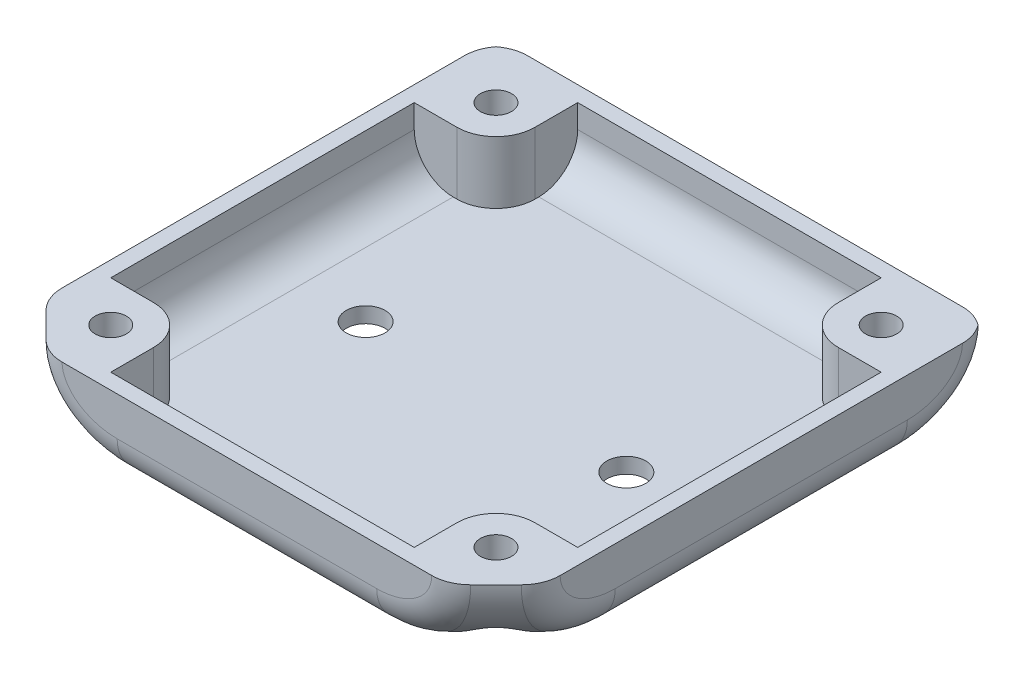
SolidWorks part; units mm, degrees
ref_plane "Front Plane" through (0, 0, 0) normal (0, 0, 1) x (1, 0, 0)
ref_plane "Top Plane" through (0, 0, 0) normal (0, 1, 0) x (1, 0, 0)
ref_plane "Right Plane" through (0, 0, 0) normal (1, 0, 0) x (0, 0, -1)
sketch "Sketch1" plane through (0, 0, 0) normal (0, 1, 0) x (1, 0, 0)
  line L1 (-32, -32) -> (32, -32)
  line L2 (-32, -32) -> (-32, 32)
  line L3 (-32, 32) -> (32, 32)
  line L4 (32, -32) -> (32, 32)
  line L5 (-32, -32) -> (32, 32) construction
  line L6 (-32, 32) -> (32, -32) construction
  point P0 (0, 0)
  dimension "D1" = 64
  dimension "D2" = 64
extrude "Boss-Extrude1" add sketch "Sketch1" along normal blind 2
sketch "Sketch2" plane through (0, 2, 0) normal (0, 1, 0) x (1, 0, 0)
  line L1 (-32, -32) -> (32, -32)
  line L2 (-32, -32) -> (-32, 32)
  line L3 (-32, 32) -> (32, 32)
  line L4 (32, -32) -> (32, 32)
  line L5 (-32, -32) -> (32, 32) construction
  line L6 (-32, 32) -> (32, -32) construction
  line L7 (-30, -30) -> (30, -30)
  line L8 (-30, -30) -> (-30, 30)
  line L9 (-30, 30) -> (30, 30)
  line L10 (30, -30) -> (30, 30)
  line L11 (-30, -30) -> (30, 30) construction
  line L12 (-30, 30) -> (30, -30) construction
  point P0 (0, 0)
  point P7 (0, 0)
  dimension "D1" = 2
  dimension "D2" = 2
extrude "Boss-Extrude2" add sketch "Sketch2" along normal blind 8
sketch "Sketch3" plane through (0, 0, 0) normal (0, -1, 0) x (1, 0, 0)
  line L0 (32, 32) -> (32, -32) construction
  line L5 (-22, 32) -> (-32, 32)
  line L7 (-32, 32) -> (32, 32) construction
  line L14 (32, 32) -> (22, 32)
  line L15 (-32, 22) -> (-22, 32)
  line L16 (22, 32) -> (32, 22)
  line L22 (32, 32) -> (27, 27) construction
  line L23 (-27, 27) -> (-32, 32) construction
  line L27 (-32, 22) -> (-32, 32)
  line L30 (32, 22) -> (32, 32)
  point P0 (0, 0)
  point P10 (0, 0)
  point P18 (0, 0)
extrude "Cut-Extrude1" cut sketch "Sketch3" against normal blind 10
sketch "Sketch4" plane through (0, 0, 0) normal (0, -1, 0) x (1, 0, 0)
  line L0 (-32, 22) -> (-22, 32)
  line L3 (-32, 25.8184) -> (-25.8184, 32)
  line L4 (22, 32) -> (32, 22)
  line L7 (25.8184, 32) -> (32, 25.8184)
  line L8 (-32, 22) -> (-32, 25.8184)
  line L9 (-22, 32) -> (-25.8184, 32)
  line L10 (22, 32) -> (25.8184, 32)
  line L11 (32, 22) -> (32, 25.8184)
  dimension "D1" = 2.7
  dimension "D2" = 2.7
extrude "Boss-Extrude3" add sketch "Sketch4" against normal through all
sketch "Sketch5" plane through (0, 0, 0) normal (0, -1, 0) x (1, 0, 0)
  line L0 (0, 0) -> (-24.7487, 24.7487) construction
  line L1 (0, 0) -> (16.0072, 0) construction
  circle A0 centre (0, 0) radius 35 construction
  circle A1 centre (-24.7487, 24.7487) radius 2
  circle A2 centre (24.7487, 24.7487) radius 2
  circle A3 centre (24.7487, -24.7487) radius 2
  circle A4 centre (-24.7487, -24.7487) radius 2
  point P15 (0, 0)
  dimension "D1" = 70
  dimension "D3" = 4
  dimension "D2" = 135
  dimension "D4" = 4
extrude "Cut-Extrude2" cut sketch "Sketch5" against normal blind 10
sketch "Sketch6" plane through (0, 0, 0) normal (0, -1, 0) x (1, 0, 0)
  line L0 (-15, 10) -> (15, 10)
  line L1 (-15, -15) -> (15, -15)
  line L2 (-15, -15) -> (-15, -10)
  line L3 (-15, 15) -> (15, 15) construction
  line L4 (15, -15) -> (15, -10)
  line L5 (-15, -15) -> (10, 10) construction
  line L6 (-10, 10) -> (15, -15) construction
  line L7 (15, 10) -> (15, 5)
  line L8 (15, 5) -> (-15, 5)
  line L9 (-15, 5) -> (-15, 0) construction
  line L10 (-15, 0) -> (15, 0)
  line L11 (15, 0) -> (15, -5)
  line L12 (15, -5) -> (-15, -5)
  line L13 (-15, -10) -> (15, -10)
  line L14 (-15, -10) -> (-15, -5) construction
  line L15 (-15, -5) -> (-15, 0)
  line L16 (15, -10) -> (15, -5) construction
  line L17 (15, -5) -> (15, 0)
  line L18 (-15, 0) -> (-15, 5) construction
  line L19 (-15, 5) -> (-15, 10)
  line L20 (15, 0) -> (15, 5) construction
  line L21 (15, 5) -> (15, 10)
  line L22 (-15, 15) -> (-10, 10) construction
  line L23 (-15, 10) -> (-15, 15) construction
  line L24 (10, 10) -> (15, 15) construction
  line L25 (15, 10) -> (15, 15) construction
  point P0 (0, 0)
  dimension "D1" = 30
  dimension "D2" = 30
  dimension "D3" = 5
  dimension "D4" = 5
  dimension "D5" = 5
  dimension "D6" = 5
  dimension "D7" = 5
extrude "Cut-Extrude3" cut sketch "Sketch6" against normal through all contours L19 L8 L7 L0 | L15 L12 L11 L10 | L13 L2 L1 L4 region at (0, 0, 7.5) region at (0, 0, -12.5) region at (0, 0, -2.5)
sketch "Sketch7" plane through (0, 0, 0) normal (0, -1, 0) x (1, 0, 0)
  line L1 (-15.5, -15.5) -> (15.5, -15.5)
  line L2 (-15.5, -15.5) -> (-15.5, 15.5)
  line L3 (-15.5, 15.5) -> (15.5, 15.5)
  line L4 (15.5, -15.5) -> (15.5, 15.5)
  line L5 (-15.5, -15.5) -> (15.5, 15.5) construction
  line L6 (-15.5, 15.5) -> (15.5, -15.5) construction
  point P0 (0, 0)
  dimension "D1" = 31
  dimension "D2" = 31
extrude "Boss-Extrude4" add sketch "Sketch7" against normal up to surface (2 mm away) up to face at (0, 2, -2.5)
sketch "Sketch8" plane through (0, 0, 0) normal (0, -1, 0) x (1, 0, 0)
  line L0 (-15.5, -15.5) -> (0, 0) construction
  line L1 (-15.5, -15.5) -> (15.5, -15.5) construction
  line L2 (-15.5, -15.5) -> (-15.5, 15.5) construction
  line L3 (-15.5, 15.5) -> (15.5, 15.5) construction
  line L4 (15.5, -15.5) -> (15.5, 15.5) construction
  line L5 (0, 0) -> (15.5, 15.5) construction
  line L6 (-15.5, 15.5) -> (0, 0) construction
  line L7 (0, 0) -> (15.5, -15.5) construction
  circle A0 centre (-15.5, 15.5) radius 2.5
  circle A1 centre (15.5, 15.5) radius 2.5
  circle A2 centre (15.5, -15.5) radius 2.5
  circle A3 centre (-15.5, -15.5) radius 2.5
  point P0 (0, 0)
  dimension "D3" = 5
  dimension "D1" = 31
  dimension "D2" = 31
extrude "Cut-Extrude4" cut sketch "Sketch8" against normal through all
sketch "Sketch9" plane through (0, 0, 0) normal (0, -1, 0) x (1, 0, 0)
  line L0 (-12.5, 12.5) -> (0, 0) construction
  line L1 (-21, -21) -> (21, -21) construction
  line L2 (-21, -21) -> (-21, 21) construction
  line L3 (-21, 21) -> (21, 21) construction
  line L4 (21, -21) -> (21, 21) construction
  line L5 (-21, -21) -> (-12.5, -12.5) construction
  line L6 (-21, 21) -> (-12.5, 12.5) construction
  line L7 (-12.5, -12.5) -> (12.5, -12.5) construction
  line L8 (-12.5, -12.5) -> (-12.5, 12.5) construction
  line L9 (-12.5, 12.5) -> (12.5, 12.5) construction
  line L10 (12.5, -12.5) -> (12.5, 12.5) construction
  line L11 (0, 0) -> (12.5, 12.5) construction
  line L12 (0, 0) -> (12.5, -12.5) construction
  line L13 (12.5, -12.5) -> (21, -21) construction
  line L14 (-12.5, 12.5) -> (0, 0) construction
  line L15 (-12.5, -12.5) -> (0, 0) construction
  line L16 (12.5, 12.5) -> (21, 21) construction
  line L17 (-12.5, -12.5) -> (0, 0) construction
  line L18 (0, 0) -> (12.5, -12.5) construction
  line L19 (0, 0) -> (12.5, 12.5) construction
  line L20 (-12.5, -12.5) -> (-12.5, 12.5) construction
  line L21 (-12.5, -12.5) -> (-21, -12.5) construction
  line L22 (-12.5, 12.5) -> (-21, 12.5) construction
  line L23 (-21, -12.5) -> (-21, 12.5) construction
  line L24 (12.5, -12.5) -> (12.5, 12.5) construction
  line L25 (12.5, -12.5) -> (21, -12.5) construction
  line L26 (12.5, 12.5) -> (21, 12.5) construction
  line L27 (21, -12.5) -> (21, 12.5) construction
  circle A0 centre (-16.75, 0) radius 2.5
  circle A1 centre (16.75, 0) radius 2.5
  point P0 (0, 0)
  point P6 (0, 0)
  dimension "D3" = 5
  dimension "D4" = 5
  dimension "D1" = 42
  dimension "D2" = 25
extrude "Cut-Extrude5" cut sketch "Sketch9" against normal through all contours A0 | A1
sketch "Sketch10" plane through (0, 2, 0) normal (0, 1, 0) x (1, 0, 0)
  line L0 (-30, -24) -> (-24, -30)
  line L3 (-19.4975, 30) -> (-30, 30)
  line L4 (-30, 19.4975) -> (-30, 30)
  line L5 (27, -27) -> (-30, 30) construction
  line L6 (30, 30) -> (-27, -27) construction
  line L7 (19.4975, 19.4975) -> (30, 19.4975)
  line L8 (24, -30) -> (30, -24)
  line L9 (19.4975, 30) -> (30, 30)
  line L10 (-30, 19.4975) -> (-19.4975, 19.4975)
  line L11 (-30, 19.4975) -> (-30, 30)
  line L12 (-30, 30) -> (-19.4975, 30)
  line L13 (-19.4975, 19.4975) -> (-19.4975, 30)
  line L14 (-30, 19.4975) -> (-19.4975, 30) construction
  line L15 (-30, 30) -> (-19.4975, 19.4975) construction
  line L16 (19.4975, 30) -> (19.4975, 19.4975)
  line L17 (30, 19.4975) -> (30, 30)
  line L18 (19.4975, -19.4975) -> (19.4975, -30)
  line L19 (30, -19.4975) -> (30, -24)
  line L20 (30, -19.4975) -> (19.4975, -19.4975)
  line L21 (19.4975, -30) -> (24, -30)
  line L22 (-19.4975, -19.4975) -> (-30, -19.4975)
  line L23 (-19.4975, -30) -> (-24, -30)
  line L24 (-19.4975, -30) -> (-19.4975, -19.4975)
  line L25 (-30, -19.4975) -> (-30, -24)
  circle A1 centre (-24.7487, 24.7487) radius 2
  circle A2 centre (24.7487, 24.7487) radius 2
  circle A3 centre (24.7487, -24.7487) radius 2
  circle A4 centre (-24.7487, -24.7487) radius 2
  point P0 (0, 0)
  point P2 (-24.7487, 24.7487)
  point P36 (0, 0)
  line M25 (-24, -30) -> (24, -30)
  line M26 (24, -30) -> (30, -24)
  line M27 (30, -24) -> (30, 30)
  line M28 (30, 30) -> (-30, 30)
  line M29 (-30, 30) -> (-30, -24)
  line M30 (-30, -24) -> (-24, -30)
  circle M31 centre (-24.7487, -24.7487) radius 2
  circle M32 centre (24.7487, -24.7487) radius 2
  circle M33 centre (24.7487, 24.7487) radius 2
  circle M34 centre (-24.7487, 24.7487) radius 2
  dimension "D1" = 4
extrude "Boss-Extrude5" add sketch "Sketch10" along normal through all contours L10 L13 M28 M29 M34 | L16 L7 M28 M27 M33 | L24 L22 M25 M29 M30 M31 | L20 L18 M27 M25 M26 M32 region at (-29.8515, 2, 21.7487) region at (-29.8515, 2, -24.7487) region at (19.646, 2, 24.7487) region at (24.7487, 2, -29.8515)
sketch "Sketch11" plane through (0, 0, 0) normal (0, -1, 0) x (1, 0, 0)
  circle A0 centre (-24.7487, 24.7487) radius 3.6
  circle A1 centre (24.7487, 24.7487) radius 3.6
  circle A2 centre (24.7487, -24.7487) radius 3.6
  circle A3 centre (-24.7487, -24.7487) radius 3.6
  point P12 (0, 0)
  dimension "D1" = 7.2
  dimension "D2" = 4
extrude "Cut-Extrude6" cut sketch "Sketch11" against normal offset from surface (7 mm away) 3 up to face at (0, 10, 0)
fillet "Fillet1" radius 5 4 edges at (-19.4975, 6, 19.4975) (19.4975, 6, 19.4975) (19.4975, 6, -19.4975) (-19.4975, 6, -19.4975)
sketch "Sketch12" plane through (0, 0, 0) normal (0, -1, 0) x (1, 0, 0)
  circle A0 centre (-15.5, -15.5) radius 3.72
  circle A1 centre (-15.5, 15.5) radius 3.5401
  circle A2 centre (15.5, 15.5) radius 4.3135
  circle A3 centre (15.5, -15.5) radius 4.1056
extrude "Boss-Extrude6" add sketch "Sketch12" against normal up to surface (2 mm away) up to face at (-16.75, 2, -2.5)
chamfer "Chamfer1" distance 2 angle 45 2 edges at (-32, 5, -32) (32, 5, -32)
fillet "Fillet2" radius 10 4 edges at (-31, 0, -31) (31, 0, -31) (28.9092, 0, 28.9092) (-28.9092, 0, 28.9092)
fillet "Fillet3" radius 5 12 edges at (25.8579, 2.9289, -32) (-25.8579, 2.9289, -32) (32, 2.9289, 21.6762) (32, 2.9289, -25.8579) (-21.6762, 2.9289, 32) (21.6762, 2.9289, 32) (-32, 2.9289, -25.8579) (-32, 2.9289, 21.6762) (0, 0, -32) (32, 0, -2.0908) (0, 0, 32) (-32, 0, -2.0908)
fillet "Fillet4" radius 5 4 edges at (0, 2, 30) (-30, 2, 0) (0, 2, -30) (30, 2, 0)
sketch "Sketch13" plane through (0, 0, 0) normal (0, -1, 0) x (1, 0, 0)
  line L0 (0, 0) -> (11.3, 0) construction
  line L1 (0, 0) -> (7.9903, 7.9903) construction
  circle A0 centre (0, 0) radius 11.3 construction
  circle A1 centre (7.9903, 7.9903) radius 2
  circle A3 centre (7.9903, -7.9903) radius 2
  circle A4 centre (-7.9903, -7.9903) radius 2
  circle A5 centre (-7.9903, 7.9903) radius 2
  point P11 (0, 0)
  point P16 (0, 0)
  dimension "D1" = 22.6
  dimension "D3" = 4
  dimension "D2" = 45
  dimension "D4" = 4
